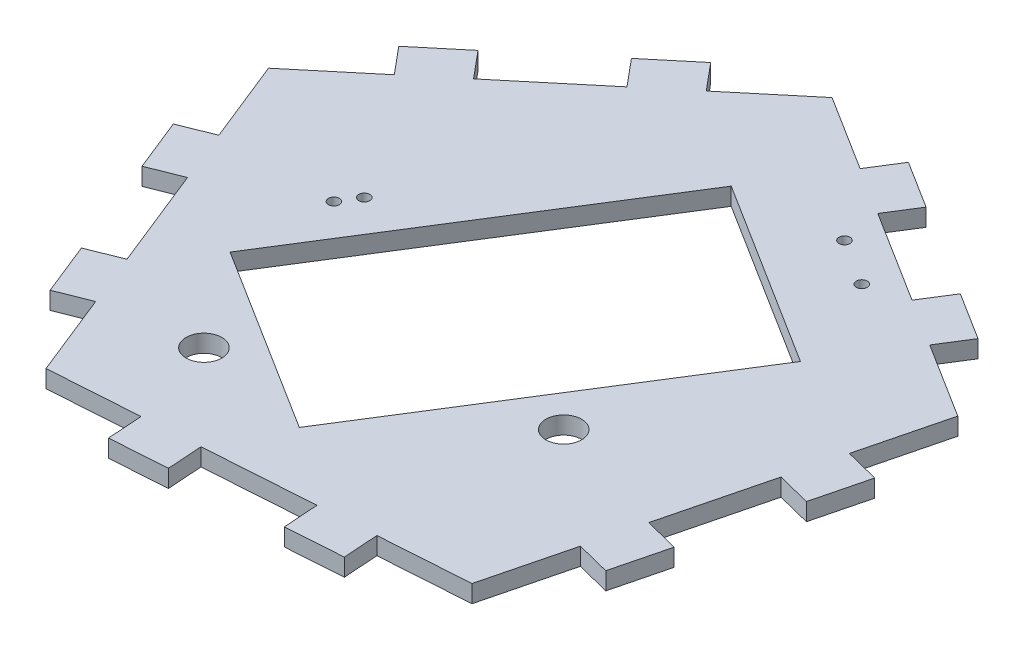
SolidWorks part; units mm, degrees
ref_plane "Front Plane" through (0, 0, 0) normal (0, 0, 1) x (1, 0, 0)
ref_plane "Top Plane" through (0, 0, 0) normal (0, 1, 0) x (1, 0, 0)
ref_plane "Right Plane" through (0, 0, 0) normal (1, 0, 0) x (0, 0, -1)
sketch "Sketch1" plane through (0, 0, 0) normal (0, 1, 0) x (1, 0, 0)
  line L1 (-59.9258, 15.1181) -> (-32.8962, -52.3211)
  line L2 (-32.8962, -52.3211) -> (39.5948, -47.4543)
  line L3 (39.5948, -47.4543) -> (57.3672, 22.9927)
  line L4 (57.3672, 22.9927) -> (-4.14, 61.6646)
  line L5 (-4.14, 61.6646) -> (-59.9258, 15.1181)
  circle A0 centre (0, 0) radius 50 construction
  dimension "D1" = 100
extrude "Boss-Extrude1" add sketch "Sketch1" along normal blind 3.18
ref_axis "Axis" through (0, 3.339, 0) along (0, -1, 0)
sketch "Axis Check" plane through (0, 3.18, 0) normal (0, 1, 0) x (1, 0, 0)
  line L0 (3.3493, -49.8877) -> (-4.14, 61.6646) construction
  line L1 (-32.8962, -52.3211) -> (39.5948, -47.4543) construction
  line L2 (57.3672, 22.9927) -> (-46.411, -18.6015) construction
  line L3 (-59.9258, 15.1181) -> (-32.8962, -52.3211) construction
  line L4 (-32.0329, 38.3913) -> (39.5948, -47.4543) construction
  line L5 (-4.14, 61.6646) -> (-59.9258, 15.1181) construction
  line L6 (-59.9258, 15.1181) -> (48.481, -12.2308) construction
  line L7 (39.5948, -47.4543) -> (57.3672, 22.9927) construction
  line L8 (-32.8962, -52.3211) -> (26.6136, 42.3287) construction
  line L9 (57.3672, 22.9927) -> (-4.14, 61.6646) construction
sketch "Sketch2" plane through (0, 0, 0) normal (0, -1, 0) x (1, 0, 0)
  line L0 (-53.8107, 0.1392) -> (-47.9072, -2.2269)
  line L1 (-53.8107, 0.1392) -> (-50.1723, 9.2172)
  line L2 (-47.9072, -2.2269) -> (-44.2688, 6.8511)
  line L3 (-50.1723, 9.2172) -> (-44.2688, 6.8511)
  line L4 (-59.9258, -15.1181) -> (-32.8962, 52.3211) construction
  line L5 (-42.6498, 27.9858) -> (-39.0113, 37.0638)
  line L6 (-42.6498, 27.9858) -> (-36.7463, 25.6197)
  line L7 (-39.0113, 37.0638) -> (-33.1079, 34.6977)
  line L8 (-36.7463, 25.6197) -> (-33.1079, 34.6977)
  line L9 (-46.411, 18.6015) -> (-19.2439, 7.7129) construction
  line L10 (-40.8306, 32.5248) -> (-34.9271, 30.1587) construction
  dimension "D1" = 6.36
  dimension "D2" = 9.78
  dimension "D3" = 10.11
extrude "Cut F" [suppressed] cut sketch "Sketch2" against normal through all
sketch "Sketch4" plane through (0, 3.18, 0) normal (0, 1, 0) x (1, 0, 0)
  line L9 (26.6136, 42.3287) -> (-26.6136, -42.3287) construction
  line L10 (57.3672, 22.9927) -> (-4.14, 61.6646) construction
  line L11 (-34.4964, -17.2915) -> (0.6335, 38.5824)
  line L12 (-34.4964, -17.2915) -> (-0.6335, -38.5824)
  line L13 (0.6335, 38.5824) -> (34.4964, 17.2915)
  line L14 (-0.6335, -38.5824) -> (34.4964, 17.2915)
  line L15 (-34.4964, -17.2915) -> (34.4964, 17.2915) construction
  line L16 (0.6335, 38.5824) -> (-0.6335, -38.5824) construction
  line L20 (0, 0) -> (39.0006, -24.5211) construction
  circle A0 centre (-21.8232, -34.7095) radius 3.25
  circle A1 centre (23.7041, -14.9036) radius 3.25
  point P5 (0, 0)
  point P6 (-21.8232, -34.7095)
  dimension "D3" = 6.5
  dimension "D1" = 40
  dimension "D2" = 66
  dimension "D4" = 8
  dimension "D5" = 8
extrude "Top Cut" cut sketch "Sketch4" against normal blind 10
sketch "Sketch7" plane through (0, 3.18, 0) normal (0, 1, 0) x (1, 0, 0)
  line L0 (0, 0) -> (26.6136, 42.3287) construction
  line L1 (57.3672, 22.9927) -> (-4.14, 61.6646) construction
  line L2 (-7.1857, -11.4287) -> (-30.8897, 3.4749) construction
  line L3 (-14.3588, -11.6437) -> (-33.0188, 0.0886) construction
  line L5 (0.6335, 38.5824) -> (-34.4964, -17.2915) construction
  circle A0 centre (-30.8897, 3.4749) radius 1
  circle A1 centre (-33.0188, 0.0886) radius 1
  dimension "D5" = 2
  dimension "D1" = 4
  dimension "D2" = 17.5
  dimension "D3" = 8
  dimension "D4" = 8
extrude "Top Cut 2" cut sketch "Sketch7" against normal through all
sketch "Sketch10" plane through (0, 3.18, 0) normal (0, 1, 0) x (1, 0, 0)
  line L0 (26.6136, 42.3287) -> (17.565, 27.9369) construction
  line L1 (57.3672, 22.9927) -> (-4.14, 61.6646) construction
  line L2 (34.4964, 17.2915) -> (0.6335, 38.5824) construction
  line L3 (33.0578, 31.7802) -> (13.6147, 44.0048) construction
  line L4 (34.4964, 17.2915) -> (0.6335, 38.5824) construction
  circle A0 centre (19.4532, 40.3339) radius 1
  circle A1 centre (27.919, 35.0111) radius 1
  dimension "D1" = 11.5
  dimension "D2" = 2
  dimension "D3" = 5
extrude "Top Cut 3" cut sketch "Sketch10" against normal blind 10
sketch "Sketch8" [suppressed] plane through (0, 3.18, 0) normal (0, 1, 0) x (1, 0, 0)
  line L0 (3.3493, -49.8877) -> (-4.14, 61.6646) construction
  line L5 (-32.8962, -52.3211) -> (39.5948, -47.4543) construction
  line L6 (-17.9455, -31.2723) -> (21.9647, -28.5929)
  line L11 (-17.9455, -31.2723) -> (-21.9647, 28.5929)
  line L12 (21.9647, -28.5929) -> (17.9455, 31.2723)
  line L13 (-21.9647, 28.5929) -> (17.9455, 31.2723)
  point P4 (1.4955, -22.2759)
  dimension "D1" = 60
  dimension "D2" = 40
  dimension "D3" = 20
extrude "Bottom Cut" [suppressed] cut sketch "Sketch8" against normal blind 10
sketch "Sketch9" [suppressed] plane through (0, 3.18, 0) normal (0, 1, 0) x (1, 0, 0)
  line L0 (19.9551, 1.3397) -> (-19.9551, -1.3397) construction
  line L1 (21.9647, -28.5929) -> (17.9455, 31.2723) construction
  line L2 (-21.9647, 28.5929) -> (-17.9455, -31.2723) construction
  line L3 (-19.9551, -1.3397) -> (-44.4689, -2.9855) construction
  line L4 (19.9551, 1.3397) -> (42.6839, 2.8657) construction
  line L5 (-32.8962, -52.3211) -> (39.5948, -47.4543) construction
  line L6 (-29.6051, -6.8886) -> (-32.3788, -7.0748)
  line L7 (-29.6051, -6.8886) -> (-30.2602, 2.8694)
  line L8 (-30.2602, 2.8694) -> (-33.0339, 2.6832)
  line L9 (-32.3788, -7.0748) -> (-33.0339, 2.6832)
  line L10 (-29.6051, -6.8886) -> (-33.0339, 2.6832) construction
  line L11 (-30.2602, 2.8694) -> (-32.3788, -7.0748) construction
  line L12 (33.0339, -2.6832) -> (30.2602, -2.8694)
  line L13 (33.0339, -2.6832) -> (32.3788, 7.0748)
  line L14 (32.3788, 7.0748) -> (29.6051, 6.8886)
  line L15 (30.2602, -2.8694) -> (29.6051, 6.8886)
  line L16 (33.0339, -2.6832) -> (29.6051, 6.8886) construction
  line L17 (32.3788, 7.0748) -> (30.2602, -2.8694) construction
  line L18 (-32.8962, -52.3211) -> (39.5948, -47.4543) construction
  point P6 (-31.3195, -2.1027)
  point P13 (31.3195, 2.1027)
  dimension "D1" = 9.78
  dimension "D4" = 9.78
  dimension "D5" = 10
  dimension "D6" = 10
  dimension "D2" = 2.78
  dimension "D3" = 2.78
extrude "Battery Holder Cut" [suppressed] cut sketch "Sketch9" against normal blind 6.36
sketch "Sketch3" plane through (0, 3.18, 0) normal (0, 1, 0) x (1, 0, 0)
  line L0 (0, 0) -> (-40.9819, 49.1167) construction
  line L1 (-51.5485, 30.3911) -> (-43.3993, 20.6243)
  line L3 (-43.3993, 20.6243) -> (-35.5521, 27.1718)
  line L4 (-43.7013, 36.9386) -> (-35.5521, 27.1718)
  line L5 (-4.14, 61.6646) -> (-59.9258, 15.1181) construction
  line L6 (-71.9961, 5.0469) -> (-69.9588, 2.6052)
  line L7 (-71.9961, 5.0469) -> (-47.4739, 25.5077)
  line L14 (-28.5137, 49.6108) -> (-20.3645, 39.8441)
  line L16 (-20.3645, 39.8441) -> (-12.5173, 46.3916)
  line L17 (-20.6665, 56.1583) -> (-12.5173, 46.3916)
  line L18 (-40.5017, 25.1278) -> (-39.4757, 23.8981) construction
  line L19 (-51.5485, 30.3911) -> (-43.7013, 36.9386)
  line L21 (-28.5137, 49.6108) -> (-20.6665, 56.1583)
  line L22 (-16.5919, 51.275) -> (4.7866, 69.1127)
  line L23 (-39.6267, 32.0552) -> (-24.4391, 44.7274)
  line M18 (-4.14, 61.6646) -> (-59.9258, 15.1181)
  dimension "D1" = 12.72
  dimension "D2" = 10.22
  dimension "D3" = 9.89
  dimension "D4" = 100
extrude "Extrude M" add sketch "Sketch3" against normal up to surface (3.18 mm away) contours L21 L14 L7 L17 | L19 L1 L4 M18 region at (-45.5876, 3.18, -31.2231) region at (-22.5528, 3.18, -50.4429) up to face at (19.4532, 0, -39.3339)
pattern_circular "Circle F" [suppressed] count 5 over 360 about axis through (0, 3.339, 0) along (0, -1, 0) of bodies 102
pattern_circular "Circle M" count 5 over 360 about axis through (0, 3.339, 0) along (0, -1, 0) of "Extrude M"
pattern_circular "Circle Side F" [suppressed] count 5 over 360 about axis through (0, 3.339, 0) along (0, -1, 0) of bodies 173
pattern_circular "Circle Side M" [suppressed] count 5 over 360 about axis through (0, 3.339, 0) along (0, -1, 0) of bodies 168
equation "\"kerf\"= .22mm"
equation "\"tabWidthF\"= 10 - \"kerf\""
equation "\"tabThickness\" = 6.36mm"
equation "\"D1@Sketch2\"=\"tabThickness\""
equation "\"tabWidthM\"= 10 + \"kerf\""
equation "\"halfkerf\"= \"kerf\" / 2.00mm"
equation "\"D1@Sketch9\"=\"tabWidthF\""
equation "\"D4@Sketch9\"=\"tabWidthF\""
equation "\"D1@Battery Holder Cut\" = \"tabThickness\""
equation "\"tabLength\" = \"kerf\" + 12"
